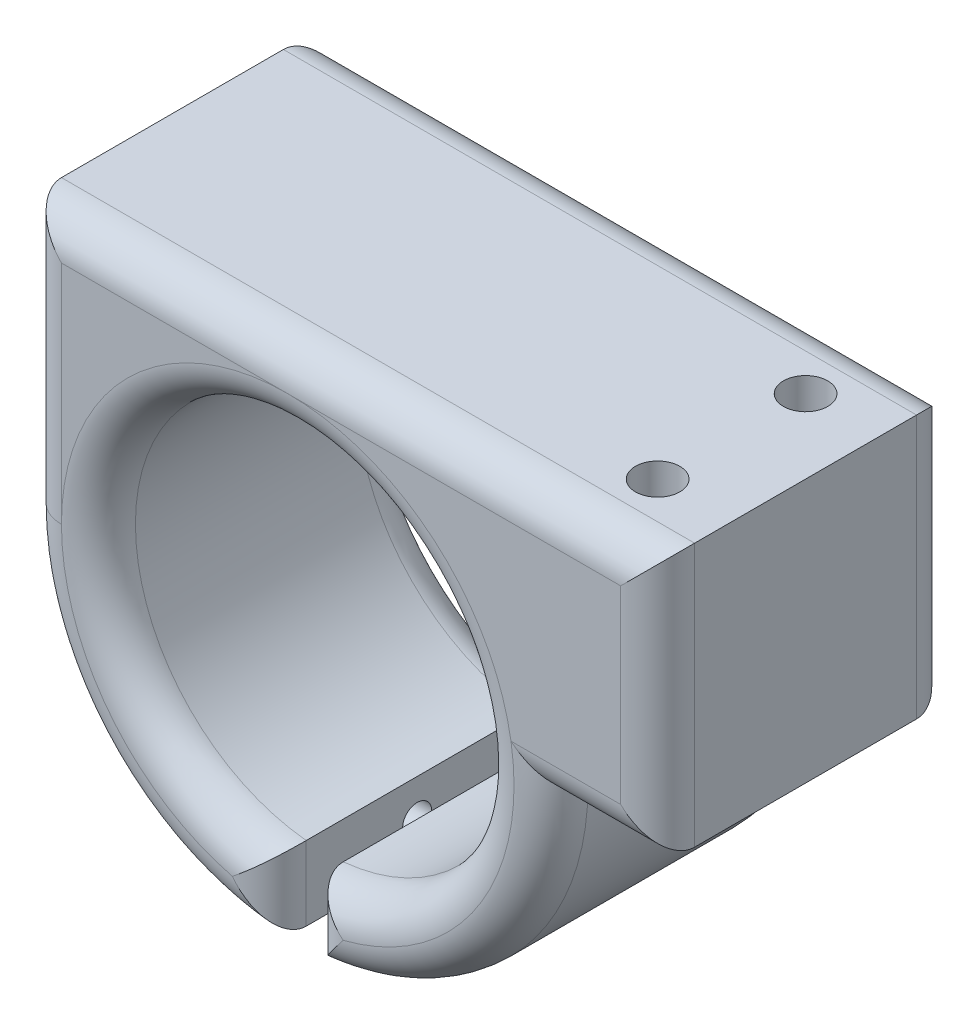
SolidWorks part; units mm, degrees
ref_plane "Front Plane" through (0, 0, 0) normal (0, 0, 1) x (1, 0, 0)
ref_plane "Top Plane" through (0, 0, 0) normal (0, 1, 0) x (1, 0, 0)
ref_plane "Right Plane" through (0, 0, 0) normal (1, 0, 0) x (0, 0, -1)
sketch "Sketch2" plane through (0, 0, 0) normal (0, 1, 0) x (1, 0, 0)
  line L0 (-31.75, -12.7) -> (-31.75, 12.7) construction
  line L1 (44.45, 25.4) -> (-44.45, 25.4)
  line L2 (44.45, 25.4) -> (44.45, -25.4)
  line L3 (44.45, -25.4) -> (-44.45, -25.4)
  line L4 (-44.45, 25.4) -> (-44.45, -25.4)
  line L5 (44.45, 25.4) -> (-44.45, -25.4) construction
  line L6 (44.45, -25.4) -> (-44.45, 25.4) construction
  line L7 (-31.75, 0) -> (0, 0) construction
  line L8 (-19.05, 25.4) -> (-19.05, -25.4)
  circle A0 centre (-31.75, 12.7) radius 3.81
  circle A1 centre (-31.75, -12.7) radius 3.81
  point P0 (0, 0)
  point P1 (0, 0)
  point P7 (115.9564, 68.2319)
  dimension "D5" = 7.62
  dimension "D1" = 88.9
  dimension "D2" = 50.8
  dimension "D3" = 12.7
  dimension "D4" = 25.4
  dimension "D6" = 12.7
extrude "Boss-Extrude1" add sketch "Sketch2" against normal blind 25.4 contours L8 L1 L4 L3 A1 A0 region at (-31.75, 0, 0)
sketch "Sketch3" plane through (0, 0, 0) normal (0, 0, 1) x (1, 0, 0)
  line L0 (-31.75, 0) -> (-31.75, -12.7) construction
  line L1 (-19.05, 0) -> (-44.45, 0) construction
  line L2 (-31.75, -12.7) -> (-82.55, -12.7) construction
  line L3 (-82.55, -12.7) -> (-82.55, -45.2) construction
  line L4 (-44.45, -25.4) -> (-44.45, 0) construction
  line L5 (-44.45, 0) -> (-127.75, 0)
  line L6 (-127.75, 0) -> (-127.75, -45.2)
  line L7 (-127.75, -45.2) -> (-115.05, -45.2)
  line L8 (-19.05, -25.4) -> (-19.05, -45.2)
  line L9 (-19.05, -45.2) -> (-50.05, -45.2)
  line L10 (-19.05, -25.4) -> (-44.45, -25.4) construction
  line L11 (-44.45, -25.4) -> (-44.45, 0)
  line L12 (-19.05, -25.4) -> (-44.45, -25.4)
  circle A0 centre (-82.55, -45.2) radius 32.5
  arc A1 (-127.75, -45.2) -> (-37.35, -45.2) centre (-82.55, -45.2) ccw
  dimension "D1" = 65
  dimension "D2" = 32.5
  dimension "D3" = 12.7
  dimension "D4" = 38.1
  dimension "D5" = 12.7
extrude "Boss-Extrude2" add sketch "Sketch3" along normal mid plane 50.8 contours A0 L9 L8 L12 L11 L5 L6 L7 | L7 A1 L9 A0 region at (-45.6272, -12.7, 0) region at (-121.4, -46.2107, 0)
sketch "Sketch4" plane through (0, 0, 25.4) normal (0, 0, 1) x (1, 0, 0)
  line L0 (-82.55, -45.2) -> (-82.55, -77.7) construction
  line L2 (-85.725, -104.5667) -> (-79.375, -104.5667)
  line L3 (-85.725, -104.5667) -> (-85.725, -50.8333)
  line L4 (-85.725, -50.8333) -> (-79.375, -50.8333)
  line L5 (-79.375, -104.5667) -> (-79.375, -50.8333)
  line L6 (-85.725, -104.5667) -> (-79.375, -50.8333) construction
  line L7 (-85.725, -50.8333) -> (-79.375, -104.5667) construction
  circle A0 centre (-82.55, -45.2) radius 32.5 construction
  circle A1 centre (-82.55, -45.2) radius 32.5
  arc M4 (-127.75, -45.2) -> (-37.35, -45.2) centre (-82.55, -45.2) ccw
  circle M7 centre (-82.55, -45.2) radius 32.5
  dimension "D1" = 6.35
extrude "Cut-Extrude1" cut sketch "Sketch4" against normal blind 170.18 contours L2 L5 L3 M4 | L5 L4 L3 M7 | L5 L3 M4 M7 region at (-82.55, -97.4647, 25.4) region at (-82.55, -84.0055, 25.4) region at (-82.55, -64.2408, 25.4)
sketch "Sketch5" plane through (-127.75, 0, 0) normal (-1, 0, 0) x (0, 0, 1)
  line L0 (25.4, -77.5445) -> (-25.4, -77.5445) construction
  line L1 (25.4, -77.5445) -> (-25.4, -77.5445)
  line L2 (25.4, -77.5445) -> (25.4, -90.2884)
  line L3 (25.4, -90.2884) -> (-25.4, -90.2884) construction
  line L4 (25.4, -90.2884) -> (-25.4, -90.2884)
  line L5 (-25.4, -77.5445) -> (-25.4, -90.2884)
  line L6 (0, -90.2884) -> (0, -77.5445) construction
  line L8 (-9.525, -88.0439) -> (9.525, -88.0439)
  line L9 (-9.525, -88.0439) -> (-9.525, -79.7889)
  line L10 (-9.525, -79.7889) -> (9.525, -79.7889)
  line L11 (9.525, -88.0439) -> (9.525, -79.7889)
  line L12 (-9.525, -88.0439) -> (9.525, -79.7889) construction
  line L13 (-9.525, -79.7889) -> (9.525, -88.0439) construction
  circle A0 centre (0, -83.9164) radius 2.5
  dimension "D1" = 5
  dimension "D2" = 19.05
  dimension "D3" = 8.255
extrude "Cut-Extrude2" cut sketch "Sketch5" against normal blind 170.18 contours L6 A0 | A0 L6 region at (-127.75, -83.9164, 0)
extrude "Cut-Extrude3" cut sketch "Sketch5<3>" against normal blind 32.004 contours L8 L11 L10 L9 A0 region at (-127.75, -83.9164, -9.3174)
sketch "Sketch5<3>" plane through (-127.75, 0, 0) normal (-1, 0, 0) x (0, 0, 1) same geometry as "Sketch5"
ref_plane "Plane1" through (-82.55, 0, 0) normal (-1, 0, 0) x (0, 0, 1)
mirror "Mirror1" about plane through (-82.55, 0, 0) normal (-1, 0, 0) of "Cut-Extrude3"
sketch "Sketch6" plane through (0, -25.4, 0) normal (0, 1, 0) x (1, 0, 0)
  circle A0 centre (-31.75, -12.7) radius 3.81 construction
  circle A1 centre (-31.75, 12.7) radius 3.81 construction
  circle A2 centre (-31.75, -12.7) radius 3.81
  circle A3 centre (-31.75, 12.7) radius 3.81
extrude "Cut-Extrude4" cut sketch "Sketch6" against normal blind 32.004
fillet "Fillet1" radius 6.35 18 edges at (-115.6147, -76.0183, 25.4) (-127.75, -22.6, 25.4) (-73.4, 0, 25.4) (-19.05, -22.6, 25.4) (-28.2, -45.2, 25.4) (-49.4853, -76.0183, 25.4) (-79.375, -83.9164, 25.4) (-82.55, -12.7, 25.4) (-85.725, -83.9164, 25.4) (-79.375, -83.9164, -25.4) (-49.4853, -76.0183, -25.4) (-28.2, -45.2, -25.4) (-19.05, -22.6, -25.4) (-73.4, 0, -25.4) (-127.75, -22.6, -25.4) (-115.6147, -76.0183, -25.4) (-85.725, -83.9164, -25.4) (-82.55, -12.7, -25.4)
